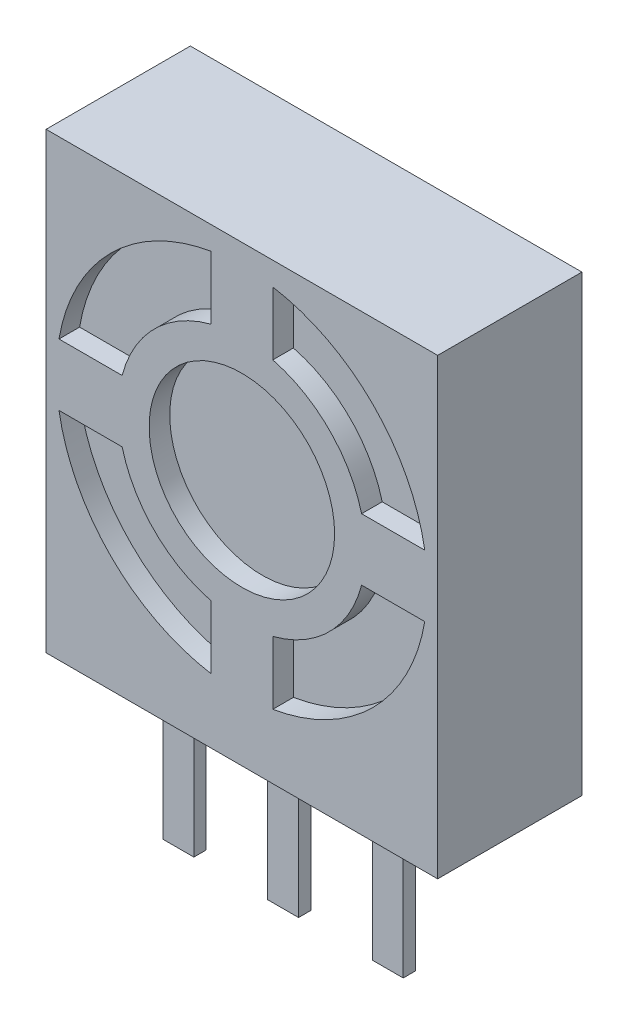
SolidWorks part; units mm, degrees
ref_plane "정면" through (0, 0, 0) normal (0, 0, 1) x (1, 0, 0)
ref_plane "윗면" through (0, 0, 0) normal (0, 1, 0) x (1, 0, 0)
ref_plane "우측면" through (0, 0, 0) normal (1, 0, 0) x (0, 0, -1)
sketch "스케치1" plane through (0, 0, 0) normal (0, 0, 1) x (1, 0, 0)
  line L1 (-4.75, -5.5) -> (4.75, -5.5)
  line L2 (-4.75, -5.5) -> (-4.75, 5.5)
  line L3 (-4.75, 5.5) -> (4.75, 5.5)
  line L4 (4.75, -5.5) -> (4.75, 5.5)
  line L5 (-4.75, -5.5) -> (4.75, 5.5) construction
  line L6 (-4.75, 5.5) -> (4.75, -5.5) construction
  point P0 (0, 0)
extrude "보스-돌출1" add sketch "스케치1" along normal blind 3.5
sketch "스케치2" plane through (0, 0, 3.5) normal (0, 0, 1) x (1, 0, 0)
  line L0 (4.75, 5.5) -> (-4.75, 5.5) construction
  line L1 (0.75, 4.9371) -> (0.75, 3.4047)
  line L2 (-0.75, 1.25) -> (0.75, 1.25) construction
  line L3 (-0.75, 1.25) -> (-0.75, -0.25) construction
  line L4 (-0.75, -0.25) -> (0.75, -0.25) construction
  line L5 (0.75, 1.25) -> (0.75, -0.25) construction
  line L6 (-0.75, 1.25) -> (0.75, -0.25) construction
  line L7 (-0.75, -0.25) -> (0.75, 1.25) construction
  line L8 (-0.75, 4.9371) -> (-0.75, 3.4047)
  line L9 (-4.4371, 1.25) -> (-2.9047, 1.25)
  line L10 (-4.4371, -0.25) -> (-2.9047, -0.25)
  line L13 (-0.75, -2.4047) -> (-0.75, -3.9371)
  line L14 (0.75, -2.4047) -> (0.75, -3.9371)
  line L15 (2.9047, -0.25) -> (4.4371, -0.25)
  line L16 (2.9047, 1.25) -> (4.4371, 1.25)
  arc A0 (-4.4371, -0.25) -> (-0.75, -3.9371) centre (0, 0.5) ccw
  arc A1 (-2.9047, -0.25) -> (-0.75, -2.4047) centre (0, 0.5) ccw
  arc A2 (2.9047, 1.25) -> (0.75, 3.4047) centre (0, 0.5) ccw
  arc A3 (4.4371, 1.25) -> (0.75, 4.9371) centre (0, 0.5) ccw
  arc A4 (-0.75, 4.9371) -> (-4.4371, 1.25) centre (0, 0.5) ccw
  arc A5 (-0.75, 3.4047) -> (-2.9047, 1.25) centre (0, 0.5) ccw
  arc A6 (0.75, -2.4047) -> (2.9047, -0.25) centre (0, 0.5) ccw
  arc A7 (0.75, -3.9371) -> (4.4371, -0.25) centre (0, 0.5) ccw
  circle A8 centre (0, 0.5) radius 2.25
  point P12 (0.75, 0.5)
  point P15 (-0.75, 0.5)
  point P18 (0, 1.25)
  point P21 (0, -0.25)
  dimension "D1" = 5
extrude "컷-돌출1" cut sketch "스케치2" against normal blind 0.5
sketch "스케치4" plane through (0, -5.5, 0) normal (0, -1, 0) x (1, 0, 0)
  line L0 (-4.75, 2.5) -> (4.75, 2.5) construction
  line L1 (-4.75, 3.5) -> (-4.75, 0) construction
  line L2 (4.75, 3.5) -> (4.75, 0) construction
  line L3 (-4.75, 3.5) -> (4.75, 3.5) construction
  line L4 (0, 0) -> (0, 3.5) construction
  line L5 (-0.375, 2.2) -> (0.375, 2.2)
  line L6 (-0.375, 2.2) -> (-0.375, 2.5)
  line L7 (-0.375, 2.5) -> (0.375, 2.5)
  line L8 (0.375, 2.2) -> (0.375, 2.5)
  point P16 (0, 2.2)
  dimension "D1" = 1
  dimension "D2" = 0.75
  dimension "D3" = 0.3
extrude "보스-돌출2" add sketch "스케치4" along normal blind 3.5 separate body
pattern_linear "선형 패턴1" count 2 spacing 2.54 along (-1, 0, 0) count 2 spacing 2.54 along (1, 0, 0) of "보스-돌출2" pattern seed only yes
ref_plane "평면1" through (0, 0, 0) normal (1, 0, 0) x (0, 0, -1)
